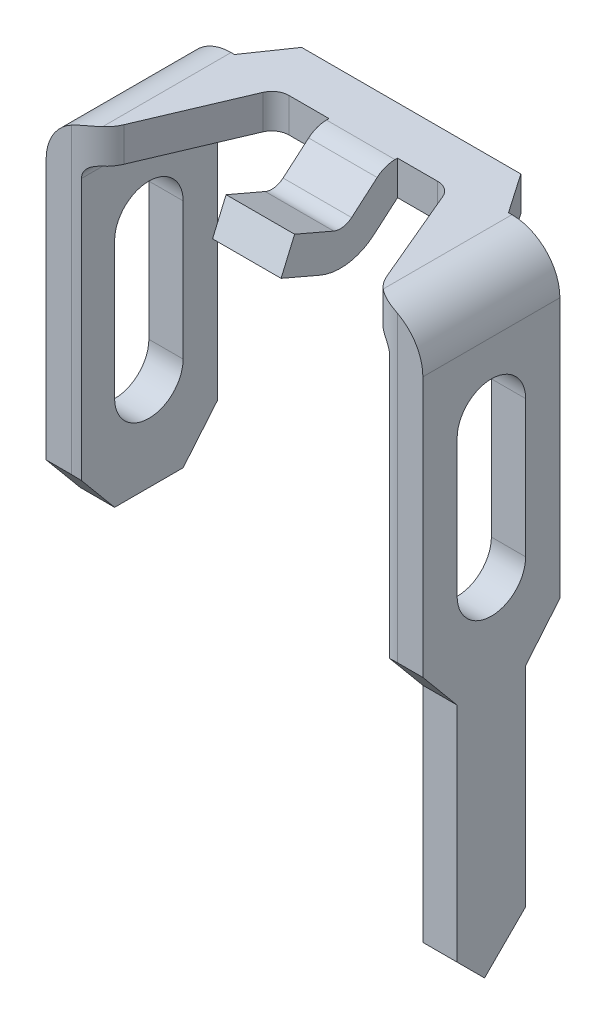
SolidWorks part; units mm, degrees
ref_plane "Front Plane" through (0, 0, 0) normal (0, 0, 1) x (1, 0, 0)
ref_plane "Top Plane" through (0, 0, 0) normal (0, 1, 0) x (1, 0, 0)
ref_plane "Right Plane" through (0, 0, 0) normal (1, 0, 0) x (0, 0, -1)
sketch "Sketch1" plane through (0, 0, 0) normal (0, 0, 1) x (1, 0, 0)
  line L0 (-2.75, -4) -> (-2.75, 4.05)
  line L1 (-2.25, -4.25) -> (-2.25, 4.25) construction
  line L2 (-2.25, -4) -> (-2.25, 4.05)
  line L3 (-2.05, 4.25) -> (2.05, 4.25)
  line L4 (2.25, -4) -> (2.25, 4.05)
  line L5 (2.2086, 4.1718) -> (2.25, 4.25) construction
  line L6 (-2.25, 4.25) -> (-2.2086, 4.1718) construction
  line L7 (-2.05, 4.75) -> (2.05, 4.75)
  line L8 (2.75, -4) -> (2.75, 4.05)
  line L9 (2.75, -4.75) -> (2.75, 4.75) construction
  line L12 (-2.75, -4.75) -> (-2.75, 4.75) construction
  line L13 (-2.25, 4.25) -> (2.25, 4.25) construction
  line L14 (-2.75, -4.75) -> (2.75, -4.75) construction
  line L15 (-2.25, -4.25) -> (2.25, -4.25) construction
  line L16 (2.25, -4.25) -> (2.25, 4.25) construction
  line L17 (-2.75, 4.75) -> (2.75, 4.75) construction
  line L18 (-2.75, -4) -> (-2.25, -4)
  line L19 (2.25, -4) -> (2.75, -4)
  arc A0 (-2.25, 4.05) -> (-2.05, 4.25) centre (-2.05, 4.05) cw
  arc A1 (2.05, 4.25) -> (2.25, 4.05) centre (2.05, 4.05) cw
  arc A2 (2.05, 4.75) -> (2.75, 4.05) centre (2.05, 4.05) cw
  arc A3 (-2.75, 4.05) -> (-2.05, 4.75) centre (-2.05, 4.05) cw
  point P0 (0, 0)
  dimension "D4" = 0.2
  dimension "D5" = 0.7
  dimension "D1" = 4.5
  dimension "D2" = 4.25
  dimension "D6" = 4
  dimension "D3" = 0.5
extrude "Boss-Extrude1" add sketch "Sketch1" along normal blind 2.58
sketch "Sketch2" plane through (0, 4.75, 0) normal (0, 1, 0) x (1, 0, 0)
  line L0 (2.05, 0) -> (-2.05, 0) construction
  line L1 (-2, -0.58) -> (-4.0994, -0.58)
  line L2 (-1.6, 0) -> (-2, 0.8334)
  line L3 (-2, 0.8334) -> (-4.0994, 0.8334)
  line L4 (-4.0994, -0.58) -> (-4.0994, 0.8334)
  line L5 (2, -0.58) -> (3.3574, -0.58)
  line L6 (1.6, 0) -> (2, 0.8334)
  line L7 (2, 0.8334) -> (3.3574, 0.8334)
  line L8 (3.3574, -0.58) -> (3.3574, 0.8334)
  line L9 (2.05, -2.58) -> (-2.05, -2.58) construction
  line L11 (-2, -0.58) -> (-1.6, 0)
  line L12 (2, -0.58) -> (1.6, 0)
  line L13 (-2.75, -2.58) -> (-2.3806, -2.58)
  line L15 (-1.9205, -2.2758) -> (-1.3147, -0.8521)
  line L16 (-1.0847, -0.7) -> (1.0843, -0.7)
  line L17 (1.3145, -0.8526) -> (1.916, -2.2748)
  line L19 (2.3765, -2.58) -> (2.75, -2.58)
  line L20 (2.75, -2.58) -> (2.75, -3.0561)
  line L21 (2.75, -3.0561) -> (-2.75, -3.0561)
  line L22 (-2.75, -3.0561) -> (-2.75, -2.58)
  arc A0 (1.916, -2.2748) -> (2.3765, -2.58) centre (2.3765, -2.08) ccw
  arc A1 (-2.3806, -2.58) -> (-1.9205, -2.2758) centre (-2.3806, -2.08) ccw
  arc A2 (1.0843, -0.7) -> (1.3145, -0.8526) centre (1.0843, -0.95) cw
  arc A3 (-1.3147, -0.8521) -> (-1.0847, -0.7) centre (-1.0847, -0.95) cw
  point P22 (-2.05, -2.58)
  point P31 (1.25, -0.7)
  point P34 (-1.25, -0.7)
  dimension "D8" = 0.5
  dimension "D9" = 0.25
  dimension "D1" = 2
  dimension "D2" = 2
  dimension "D3" = 2.5
  dimension "D4" = 1.25
  dimension "D5" = 0.4
  dimension "D6" = 0.4
  dimension "D7" = 0.7
extrude "Cut-Extrude1" cut sketch "Sketch2" against normal blind 10.5
sketch "Sketch3" plane through (0, 0, 0) normal (1, 0, 0) x (0, 0, -1)
  line L0 (-1.58, -4.25) -> (-1.58, 4.05) construction
  line L2 (-2.58, 4.05) -> (-0.58, 4.05) construction
  line L3 (-0.58, 0.25) -> (-1.08, -0.35)
  line L4 (-0.58, 4.05) -> (-0.58, -4) construction
  line L5 (-1.08, -0.35) -> (-1.08, -4.3963)
  line L6 (-1.08, -4.3963) -> (-0.1303, -4.3963)
  line L7 (-0.1303, -4.3963) -> (-0.1303, 0.25)
  line L8 (-0.1303, 0.25) -> (-0.58, 0.25)
  line L9 (-2.58, 0.25) -> (-2.08, -0.35)
  line L10 (-2.58, 4.05) -> (-2.58, -4) construction
  line L11 (-2.08, -0.35) -> (-2.08, -4.8963)
  line L12 (-2.08, -4.8963) -> (-3.0703, -4.8963)
  line L13 (-3.0703, -4.8963) -> (-3.0703, 0.25)
  line L14 (-3.0703, 0.25) -> (-2.58, 0.25)
  line L15 (-2.4551, 4.75) -> (-0.58, 4.75) construction
  line L16 (-1.58, 3.0246) -> (-1.58, 1.0246) construction
  line L17 (-1.08, 3.0246) -> (-1.08, 1.0246)
  line L18 (-2.08, 3.0246) -> (-2.08, 1.0246)
  arc A0 (-1.08, 3.0246) -> (-2.08, 3.0246) centre (-1.58, 3.0246) ccw
  arc A1 (-2.08, 1.0246) -> (-1.08, 1.0246) centre (-1.58, 1.0246) ccw
  point P22 (-1.58, 2.0246)
  dimension "D8" = 0.5
  dimension "D1" = 4.5
  dimension "D2" = 4.5
  dimension "D3" = 0.5
  dimension "D4" = 0.5
  dimension "D5" = 0.6
  dimension "D6" = 0.6
  dimension "D7" = 2
extrude "Cut-Extrude2" cut sketch "Sketch3" against normal mid plane 10.5
sketch "Sketch4" plane through (0, 0, 0) normal (1, 0, 0) x (0, 0, -1)
  line L0 (-0.7, 4.25) -> (-1.0452, 3.9541)
  line L1 (-1.8294, 3.8345) -> (-2.4, 4.0797)
  line L2 (-2.4, 4.0797) -> (-2.2026, 4.5391)
  line L3 (-2.2026, 4.5391) -> (-1.632, 4.2939)
  line L4 (-1.3706, 4.3338) -> (-0.9973, 4.6537)
  line L5 (-0.7, 4.75) -> (-0.737, 4.75)
  line L6 (-0.7, 4.75) -> (-0.7, 4.25)
  arc A0 (-0.9973, 4.6537) -> (-0.737, 4.75) centre (-0.737, 4.35) cw
  arc A1 (-1.632, 4.2939) -> (-1.3706, 4.3338) centre (-1.5333, 4.5236) ccw
  arc A2 (-1.0452, 3.9541) -> (-1.8294, 3.8345) centre (-1.5333, 4.5236) cw
  point P15 (-1.4, 3.65)
  dimension "D6" = 0.4
  dimension "D7" = 0.25
  dimension "D8" = 0.75
  dimension "D1" = 0.7
  dimension "D2" = 0.6
  dimension "D3" = 1
  dimension "D4" = 0.5
  dimension "D5" = 0.5
extrude "Boss-Extrude2" add sketch "Sketch4" along normal mid plane 1
sketch "Sketch5" plane through (-2.75, 0, 0) normal (-1, 0, 0) x (0, 0, 1)
  line L1 (0.4561, -0.35) -> (2.8869, -0.35)
  line L2 (0.4561, -0.35) -> (0.4561, -5.3799)
  line L3 (0.4561, -5.3799) -> (2.8869, -5.3799)
  line L4 (2.8869, -0.35) -> (2.8869, -5.3799)
extrude "Cut-Extrude3" cut sketch "Sketch5" against normal blind 1
chamfer "Chamfer1" distance 0.6 angle 45 1 edges at (2.5, -4, 1.08)
chamfer "Chamfer2" distance 0.4 angle 45 1 edges at (2.5, -4, 2.08)
